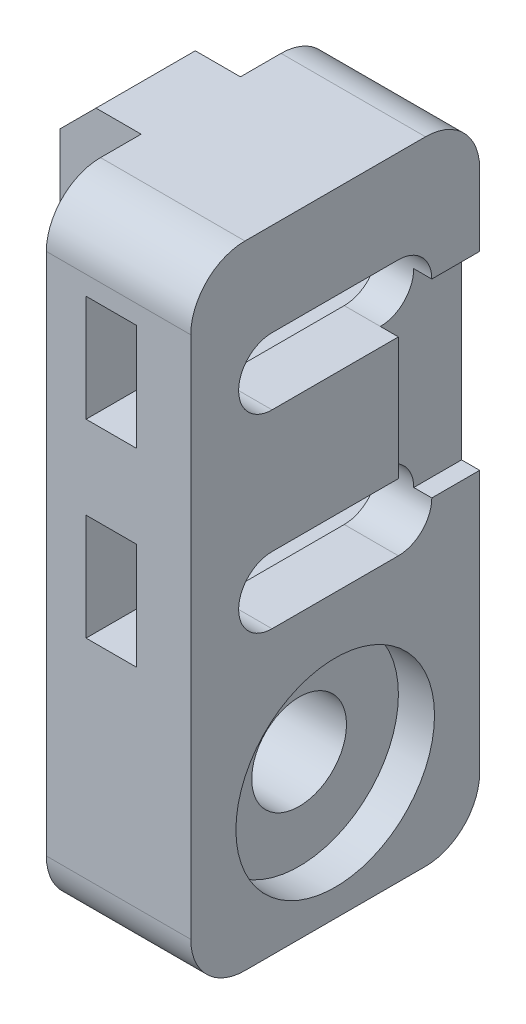
SolidWorks part; units mm, degrees
ref_plane "Front Plane" through (0, 0, 0) normal (0, 0, 1) x (1, 0, 0)
ref_plane "Top Plane" through (0, 0, 0) normal (0, 1, 0) x (1, 0, 0)
ref_plane "Right Plane" through (0, 0, 0) normal (1, 0, 0) x (0, 0, -1)
sketch "Sketch1" plane through (0, 0, 0) normal (1, 0, 0) x (0, 0, -1)
  line L0 (-32.8466, 32.9115) -> (-32.8466, -2.0885)
  line L5 (-32.8466, -2.0885) -> (-48.8466, -2.0885)
  line L6 (-48.8466, -2.0885) -> (-48.8466, 32.9115)
  line L8 (-48.8466, 32.9115) -> (-32.8466, 32.9115)
  dimension "D9" = 16
  dimension "D10" = 35
extrude "Boss-Extrude1" add sketch "Sketch1" along normal blind 8
sketch "Sketch2" plane through (0, 0, 0) normal (-1, 0, 0) x (0, 0, 1)
  line L0 (40.8466, 5.9115) -> (40.8466, 23.4488) construction
  line L1 (48.8466, 32.9115) -> (48.8466, -2.0885) construction
  line L3 (38.0966, 32.9115) -> (43.5966, 32.9115)
  line L4 (38.0966, 32.9115) -> (38.0966, 13.9861)
  line L5 (38.0966, 13.9861) -> (43.5966, 13.9861)
  line L6 (43.5966, 32.9115) -> (43.5966, 13.9861)
  line L7 (38.0966, 32.9115) -> (43.5966, 13.9861) construction
  line L8 (38.0966, 13.9861) -> (43.5966, 32.9115) construction
  line L10 (32.8466, 32.9115) -> (48.8466, 32.9115) construction
  point P5 (40.8466, 23.4488)
  dimension "D1" = 5.5
  dimension "D3" = 8
extrude "Boss-Extrude2" add sketch "Sketch2" along normal blind 4.5
chamfer "Chamfer1" distance 2 angle 45 2 edges at (-4.5, 13.9861, 40.8466) (-4.5, 32.9115, 40.8466)
sketch "Sketch7" plane through (8, 0, 0) normal (1, 0, 0) x (0, 0, -1)
  line L0 (-32.8466, -2.0885) -> (-32.8466, 32.9115) construction
  line L1 (-48.8466, 28.8615) -> (-32.8466, 28.8615)
  line L2 (-48.8466, 28.8615) -> (-48.8466, 22.9615)
  line L3 (-48.8466, 22.9615) -> (-32.8466, 22.9615)
  line L4 (-32.8466, 28.8615) -> (-32.8466, 22.9615)
  line L5 (-48.8466, 32.9115) -> (-48.8466, -2.0885) construction
  line L7 (-48.8466, 18.3615) -> (-32.8466, 18.3615)
  line L8 (-48.8466, 18.3615) -> (-48.8466, 12.4615)
  line L9 (-48.8466, 12.4615) -> (-32.8466, 12.4615)
  line L10 (-32.8466, 18.3615) -> (-32.8466, 12.4615)
  point P6 (-48.8466, 25.9115)
  dimension "D1" = 10.5
  dimension "D2" = 5.9
  dimension "D3" = 7
extrude "Cut-Extrude1" cut sketch "Sketch7" against normal blind 2.8 from offset 3 offset against normal yes
sketch "Sketch8" plane through (8, 0, 0) normal (1, 0, 0) x (0, 0, -1)
  line L0 (-44.3466, 25.9115) -> (-37.3466, 25.9115) construction
  line L1 (-44.3466, 27.7615) -> (-37.3466, 27.7615)
  line L2 (-44.3466, 24.0615) -> (-37.3466, 24.0615)
  line L3 (-44.3466, 15.4115) -> (-37.3466, 15.4115) construction
  line L4 (-44.3466, 17.2615) -> (-37.3466, 17.2615)
  line L5 (-44.3466, 13.5615) -> (-37.3466, 13.5615)
  line L6 (-32.8466, 32.9115) -> (-48.8466, 32.9115) construction
  arc A0 (-44.3466, 27.7615) -> (-44.3466, 24.0615) centre (-44.3466, 25.9115) ccw
  arc A1 (-37.3466, 24.0615) -> (-37.3466, 27.7615) centre (-37.3466, 25.9115) ccw
  arc A2 (-44.3466, 17.2615) -> (-44.3466, 13.5615) centre (-44.3466, 15.4115) ccw
  arc A3 (-37.3466, 13.5615) -> (-37.3466, 17.2615) centre (-37.3466, 15.4115) ccw
  point P2 (-40.8466, 25.9115)
  point P7 (-40.8466, 15.4115)
  point P19 (-40.8466, 32.9115)
  dimension "D4" = 1.85
  dimension "D1" = 10.5
  dimension "D2" = 7
  dimension "D3" = 7
extrude "Cut-Extrude2" cut sketch "Sketch8" against normal blind 5
sketch "Sketch9" plane through (8, 0, 0) normal (1, 0, 0) x (0, 0, -1)
  line L0 (-32.8466, -2.0885) -> (-32.8466, 32.9115) construction
  line L1 (-32.8466, 25.9115) -> (-37.3466, 25.9115)
  line L2 (-32.8466, 25.9115) -> (-32.8466, 15.4115)
  line L3 (-32.8466, 15.4115) -> (-37.3466, 15.4115)
  line L4 (-37.3466, 25.9115) -> (-37.3466, 15.4115)
extrude "Cut-Extrude3" cut sketch "Sketch9" against normal blind 1
fillet "Fillet7" radius 3 4 edges at (4, 32.9115, 32.8466) (4, 32.9115, 48.8466) (4, -2.0885, 48.8466) (4, -2.0885, 32.8466)
sketch "Sketch10" plane through (8, 0, 0) normal (1, 0, 0) x (0, 0, -1)
  line L0 (-45.8466, -2.0885) -> (-35.8466, -2.0885) construction
  circle A0 centre (-40.8466, 4.9115) radius 2.625
  dimension "D1" = 5.25
  dimension "D2" = 7
extrude "Cut-Extrude4" cut sketch "Sketch10" against normal blind 20
sketch "Sketch11" plane through (8, 0, 0) normal (1, 0, 0) x (0, 0, -1)
  circle A0 centre (-40.8466, 4.9115) radius 5.5
extrude "Cut-Extrude5" cut sketch "Sketch11" against normal blind 2
